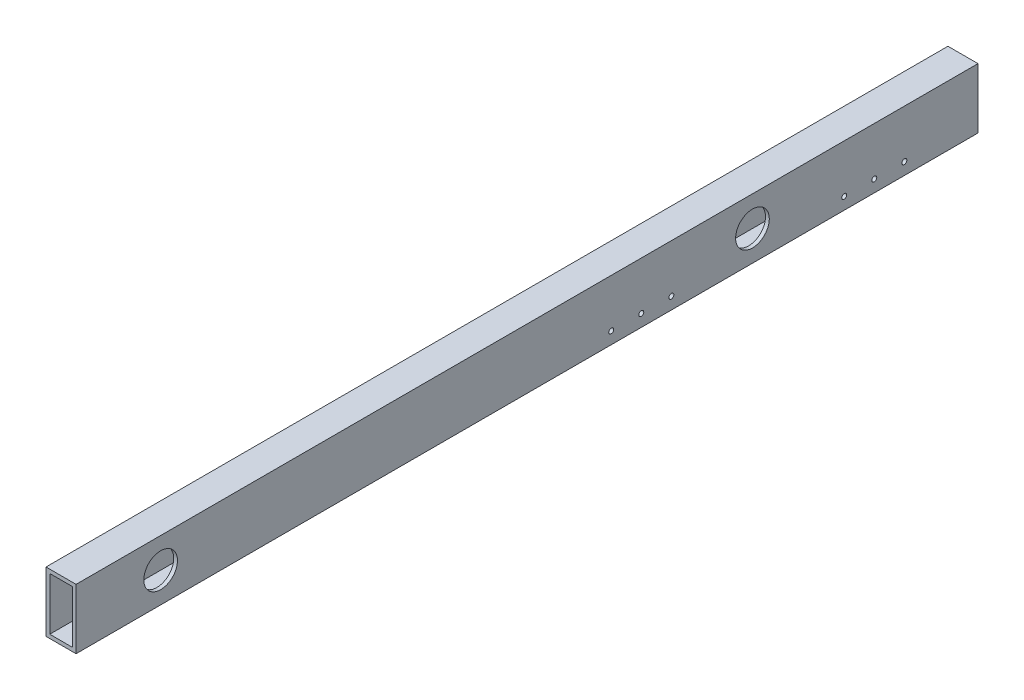
SolidWorks part; units mm, degrees
material "6061 Alloy"
ref_plane "Front Plane" through (0, 0, 0) normal (0, 0, 1) x (1, 0, 0)
ref_plane "Top Plane" through (0, 0, 0) normal (0, 1, 0) x (1, 0, 0)
ref_plane "Right Plane" through (0, 0, 0) normal (1, 0, 0) x (0, 0, -1)
sketch "Sketch1" plane through (0, 0, 0) normal (0, 0, 1) x (1, 0, 0)
  line L0 (0, 25.4) -> (0, 22.225) construction
  line L1 (-12.7, 25.4) -> (12.7, 25.4)
  line L2 (-12.7, 25.4) -> (-12.7, -25.4)
  line L3 (-12.7, -25.4) -> (12.7, -25.4)
  line L4 (12.7, 25.4) -> (12.7, -25.4)
  line L5 (-12.7, 25.4) -> (12.7, -25.4) construction
  line L6 (-12.7, -25.4) -> (12.7, 25.4) construction
  line L7 (-9.525, 22.225) -> (9.525, 22.225)
  line L8 (-9.525, 22.225) -> (-9.525, -22.225)
  line L9 (-9.525, -22.225) -> (9.525, -22.225)
  line L10 (9.525, 22.225) -> (9.525, -22.225)
  line L11 (9.525, 0) -> (12.7, 0) construction
  line L12 (-9.525, 0) -> (-12.7, 0) construction
  line L13 (0, -22.225) -> (0, -25.4) construction
  point P0 (0, 0)
  dimension "D1" = 50.8
  dimension "D2" = 25.4
  dimension "D3" = 3.175
extrude "Boss-Extrude1" add sketch "Sketch1" along normal blind 762
sketch "Sketch2" plane through (0, 25.4, 0) normal (0, 1, 0) x (1, 0, 0)
  line L0 (-26.9875, -190.549) -> (26.9875, -190.549) construction
  line L1 (-12.7, 0) -> (12.7, 0)
  line L2 (-12.7, 0) -> (-12.7, -762)
  line L3 (-12.7, -762) -> (12.7, -762)
  line L4 (12.7, 0) -> (12.7, -762)
  line L5 (-26.4963, -703.2466) -> (26.4963, -703.2466) construction
  line L6 (0, -703.2466) -> (0, -190.549) construction
  line L7 (0, 0) -> (0, -190.549) construction
  line L8 (-74.6125, -402.6047) -> (-73.6301, -528.6965) construction
  line L9 (-74.1213, -465.6506) -> (-23.8125, -465.6506) construction
  line L10 (-23.8125, -465.6506) -> (26.9875, -465.6506) construction
  dimension "D1" = 190.549
  dimension "D2" = 512.6976
  dimension "D3" = 126.0917
  dimension "D4" = 50.3088
  dimension "D5" = 50.8
  dimension "D6" = 53.975
  dimension "D7" = 52.9926
  dimension "D8" = 275.1016
ref_plane "Plane1" through (12.7, 0, 0) normal (1, 0, 0) x (0, 0, -1)
sketch "Sketch4" plane through (12.7, 0, 0) normal (1, 0, 0) x (0, 0, -1)
  line L0 (-690.548, 25.4) -> (-690.548, 0) construction
  line L1 (-703.2466, 25.4) -> (-190.549, 25.4) construction
  line L2 (-190.549, 25.4) -> (-190.549, 0) construction
  line L3 (0, 25.4) -> (-190.549, 25.4) construction
  line L4 (-190.549, 0) -> (0, 0) construction
  line L5 (0, -25.4) -> (0, 25.4) construction
  line L6 (-190.549, 0) -> (-690.548, 0) construction
  circle A0 centre (-690.548, 0) radius 14.224
  circle A1 centre (-190.549, 0) radius 14.224
  dimension "D1" = 28.448
  dimension "D2" = 499.999
  dimension "D3" = 190.549
extrude "Cut-Extrude1" cut sketch "Sketch4" against normal up to surface (25.4 mm away) contours A1 | A0 up to face at (-12.7, 0, 381)
sketch "Sketch5" plane through (0, -25.4, 0) normal (0, -1, 0) x (1, 0, 0)
  line L0 (-12.7, 0) -> (-12.7, 762) construction
  line L2 (0, 264.16) -> (0, 328.0394) construction
  line L4 (-12.7, 264.16) -> (12.7, 264.16) construction
  line L5 (12.7, 0) -> (12.7, 762) construction
  line L6 (2.54, 264.16) -> (2.54, 340.36) construction
  line L7 (0, 703.2466) -> (0, 190.549) construction
  circle A0 centre (2.54, 264.16) radius 2.0955
  circle A1 centre (2.54, 289.56) radius 2.0955
  circle A2 centre (2.54, 314.96) radius 2.0955
  circle A3 centre (-2.54, 264.16) radius 2.0955
  circle A4 centre (-2.54, 289.56) radius 2.0955
  circle A5 centre (-2.54, 314.96) radius 2.0955
  dimension "D4" = 4.191
  dimension "D1" = 264.16
  dimension "D3" = 76.2
  dimension "D6" = 10.16
  dimension "D5" = 3
extrude "Cut-Extrude2" cut sketch "Sketch5" against normal up to surface (3.175 mm away) up to face at (0, -22.225, 381)
sketch "Sketch7" plane through (12.7, 0, 0) normal (1, 0, 0) x (0, 0, -1)
  line L0 (0, -15.24) -> (-25.4, -15.24) construction
  line L1 (0, -25.4) -> (0, 25.4) construction
  line L2 (-259.08, -15.24) -> (-297.18, -15.24) construction
  line L3 (-762, -25.4) -> (0, -25.4) construction
  line L4 (-149.86, -15.24) -> (-25.4, -15.24) construction
  line L5 (-149.86, -15.24) -> (-259.08, -15.24) construction
  circle A0 centre (-259.08, -15.24) radius 2.0955
  circle A1 centre (-284.48, -15.24) radius 2.0955
  circle A2 centre (-309.88, -15.24) radius 2.0955
  circle A3 centre (-87.63, -15.24) radius 2.0955
  circle A4 centre (-62.23, -15.24) radius 2.0955
  circle A5 centre (-113.03, -15.24) radius 2.0955
  dimension "D3" = 4.191
  dimension "D1" = 259.08
  dimension "D2" = 38.1
  dimension "D5" = 10.16
  dimension "D6" = 124.46
  dimension "D7" = 25.4
  dimension "D4" = 3
  dimension "D8" = 2
  dimension "D9" = 2
extrude "Cut-Extrude3" cut sketch "Sketch7" against normal up to surface (25.4 mm away) up to face at (-12.7, 0, 176.325)
